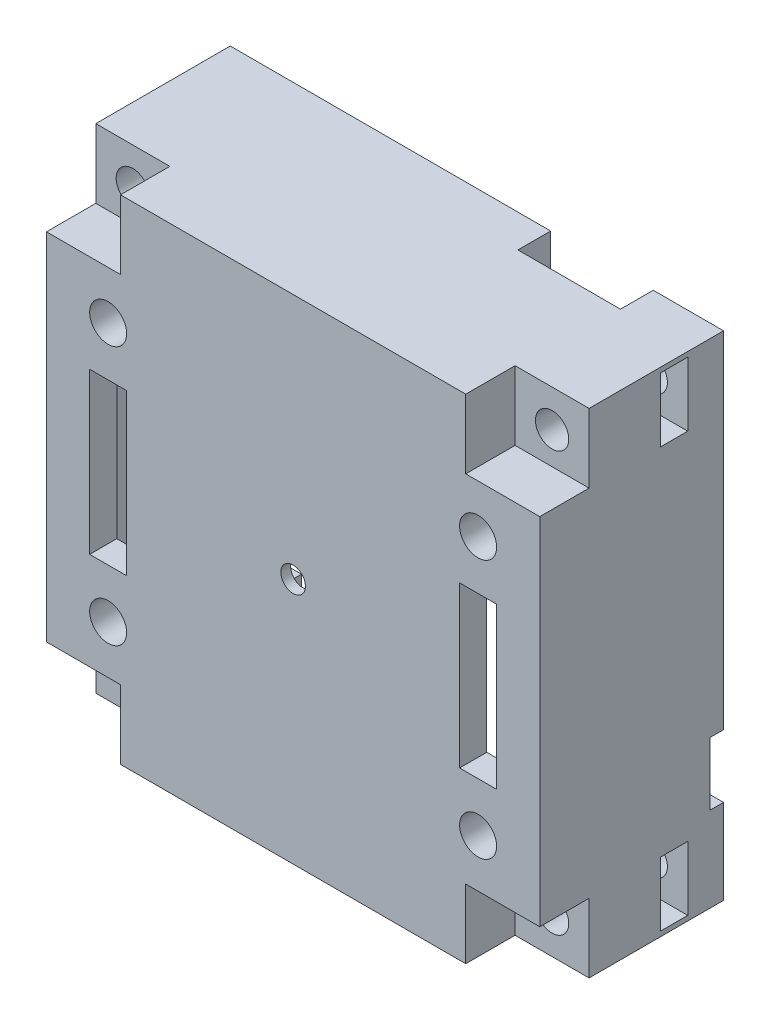
SolidWorks part; units mm, degrees
ref_plane "前视基准面" through (0, 0, 0) normal (0, 0, 1) x (1, 0, 0)
ref_plane "上视基准面" through (0, 0, 0) normal (0, 1, 0) x (1, 0, 0)
ref_plane "右视基准面" through (0, 0, 0) normal (1, 0, 0) x (0, 0, -1)
ref_plane "基准面1" through (0, 0, -12.4) normal (0, 0, -1) x (-1, 0, 0)
sketch "草图1" plane through (0, 0, -12.4) normal (0, 0, -1) x (-1, 0, 0)
  line L0 (1.7705, -8.8673) -> (1.7705, 31.1327)
  line L1 (1.7705, 31.1327) -> (-38.2295, 31.1327)
  line L2 (-38.2295, 31.1327) -> (-38.2295, -8.8673)
  line L3 (-38.2295, -8.8673) -> (1.7705, -8.8673)
  point P6 (-18.2295, 11.1327)
extrude "凸台-拉伸1" add sketch "草图1" against normal blind 12.7
ref_plane "基准面2" through (0, 0, -8) normal (0, 0, 1) x (1, 0, 0)
sketch "草图2" plane through (0, 0, -8) normal (0, 0, 1) x (1, 0, 0)
  line L0 (-2.0183, -8.4692) -> (2.7317, -8.4692)
  line L1 (2.7317, -8.4692) -> (4.2317, -5.8712)
  line L2 (4.2317, -5.8712) -> (2.7295, -3.2692)
  line L3 (2.7295, -3.2692) -> (-2.0183, -3.2692)
  line L4 (-2.0183, -3.2692) -> (-2.0183, -8.4692)
  line L5 (-1.7705, -8.8673) -> (-1.7705, 31.1327) construction
  line L6 (38.2295, -8.8673) -> (-1.7705, -8.8673) construction
  line L7 (2.7317, -8.4692) -> (-2.4592, 0.5217) construction
  line L9 (18.2295, 53.4111) -> (18.2295, -31.5909) construction
  line L10 (63.1299, 11.1327) -> (-18.8321, 11.1327) construction
  line L11 (-2.0183, 25.5346) -> (-2.0183, 30.7346)
  line L12 (2.7295, 25.5346) -> (-2.0183, 25.5346)
  line L13 (38.4773, 30.7346) -> (33.7273, 30.7346)
  line L14 (33.7273, 30.7346) -> (32.2273, 28.1365)
  line L15 (32.2273, 28.1365) -> (33.7295, 25.5346)
  line L16 (33.7295, 25.5346) -> (38.4773, 25.5346)
  line L21 (4.2317, 28.1365) -> (2.7295, 25.5346)
  line L22 (2.7317, 30.7346) -> (4.2317, 28.1365)
  line L23 (-2.0183, 30.7346) -> (2.7317, 30.7346)
  line L24 (38.4773, 25.5346) -> (38.4773, 30.7346)
  line L25 (38.4773, -3.2692) -> (38.4773, -8.4692)
  line L26 (33.7295, -3.2692) -> (38.4773, -3.2692)
  line L27 (32.2273, -5.8712) -> (33.7295, -3.2692)
  line L28 (33.7273, -8.4692) -> (32.2273, -5.8712)
  line L29 (38.4773, -8.4692) -> (33.7273, -8.4692)
  line L30 (-2.5019, -12.3303) -> (2.7295, -3.2692) construction
  point P26 (1.2295, -5.8673)
  point P34 (1.2295, -5.8673)
  dimension "D2" = 3
  dimension "D3" = 3
  dimension "D4" = 60
  dimension "D5" = 60
  dimension "D6" = 4.75
  dimension "D8" = 120
  dimension "D9" = 120
  dimension "D11" = 5.2
  dimension "D13" = 3
extrude "切除-拉伸2" cut sketch "草图2" against normal blind 1.5 and the other way blind 0.7
ref_plane "基准面3" through (0, 0, -5) normal (0, 0, -1) x (-1, 0, 0)
sketch "草图8" plane through (0, 0, -12.4) normal (0, 0, -1) x (-1, 0, 0)
  line L0 (-0.0295, 25.3327) -> (-36.4295, 25.3327)
  line L1 (-36.4295, 25.3327) -> (-36.4295, -3.0673)
  line L2 (-36.4295, -3.0673) -> (-0.0295, -3.0673)
  line L3 (-0.0295, -3.0673) -> (-0.0295, 25.3327)
extrude "切除-拉伸4" cut sketch "草图8" against normal up to surface (12.7 mm away) up to face at (18.2295, 11.1327, 0.3)
sketch "草图10" plane through (0, 0, 0.3) normal (0, 0, 1) x (1, 0, 0)
  line L1 (0.0295, 25.3327) -> (0.0295, -3.0673) construction
  line L2 (0.0295, -3.0673) -> (36.4295, -3.0673) construction
  line L3 (-1.7705, 25.5346) -> (4.2317, 25.5346)
  line L9 (36.4295, 25.3327) -> (0.0295, -3.0673) construction
  line L10 (36.4295, -3.0673) -> (0.0295, 25.3327) construction
  line L15 (36.4295, 25.3327) -> (0.0295, -3.0673) construction
  line L16 (36.4295, -3.0673) -> (0.0295, 25.3327) construction
  line L17 (4.2317, 25.5346) -> (4.2317, 31.1327)
  line L18 (-1.7705, 31.1327) -> (38.2295, 31.1327) construction
  line L19 (4.2317, 31.1327) -> (32.2273, 31.1327)
  line L20 (-1.7705, 25.5346) -> (-1.7705, -3.2692)
  line L21 (38.2295, 31.1327) -> (38.2295, -8.8673) construction
  line L31 (32.2273, 25.5346) -> (32.2273, 31.1327)
  line L48 (40.0436, 11.1327) -> (-13.5796, 11.1327) construction
  line L53 (22.8295, 16.6327) -> (13.6295, 5.6327) construction
  line L54 (22.8295, 5.6327) -> (13.6295, 16.6327) construction
  line L55 (1.7295, 17.6327) -> (4.7295, 17.6327)
  line L56 (18.2295, 36.1745) -> (18.2295, -22.808) construction
  line L57 (1.7295, 4.6327) -> (1.7295, 17.6327)
  line L58 (4.7295, 4.6327) -> (1.7295, 4.6327)
  line L59 (4.7295, 17.6327) -> (4.7295, 4.6327)
  line L60 (31.7295, 17.6327) -> (31.7295, 4.6327)
  line L61 (31.7295, 4.6327) -> (34.7295, 4.6327)
  line L62 (34.7295, 4.6327) -> (34.7295, 17.6327)
  line L63 (34.7295, 17.6327) -> (31.7295, 17.6327)
  line L64 (3.2295, 0.6327) -> (3.2295, 21.6327) construction
  line L65 (38.2295, 25.5346) -> (32.2273, 25.5346)
  line L66 (38.2295, 25.5346) -> (38.2295, -3.2692)
  line L67 (-1.7705, -3.2692) -> (4.2317, -3.2692)
  line L68 (4.2317, -3.2692) -> (4.2317, -8.8673)
  line L69 (4.2317, -8.8673) -> (32.2273, -8.8673)
  line L70 (32.2273, -3.2692) -> (32.2273, -8.8673)
  line L71 (38.2295, -3.2692) -> (32.2273, -3.2692)
  line L72 (17.7295, 10.6327) -> (18.7295, 11.6327) construction
  line L73 (17.7295, 11.6327) -> (18.7295, 10.6327) construction
  circle A0 centre (18.2295, 11.1327) radius 0.5
  circle A16 centre (3.2295, 0.6327) radius 1.5
  circle A17 centre (3.2295, 21.6327) radius 1.5
  circle A18 centre (33.2295, 21.6327) radius 1.5
  circle A19 centre (33.2295, 0.6327) radius 1.5
  point P11 (18.2295, 11.1327)
  point P12 (18.2295, 11.1327)
  point P13 (18.2295, 11.1327)
  point P25 (18.2295, 31.1327)
  point P26 (18.2295, 11.1327)
  point P33 (-1.7705, 11.1327)
  point P42 (38.2295, 11.1327)
  dimension "D5" = 13
  dimension "D6" = 3
  dimension "D7" = 3
  dimension "D11" = 1
  dimension "D1" = 21
  dimension "D2" = 30
  dimension "D3" = 11
  dimension "D4" = 9.2
  dimension "D8" = 3
  dimension "D9" = 1
  dimension "D10" = 1
extrude "凸台-拉伸2" add sketch "草图10" along normal blind 2.2 separate body
sketch "草图13" plane through (0, 0, -12.4) normal (0, 0, -1) x (-1, 0, 0)
  line L0 (10.4025, 11.1327) -> (-53.3827, 11.1327) construction
  line L3 (-18.2295, -16.9604) -> (-18.2295, 39.7747) construction
  circle A0 centre (-35.2295, -5.8673) radius 1.35
  circle A1 centre (-1.2295, -5.8673) radius 1.35
  circle A2 centre (-1.2295, 28.1327) radius 1.35
  circle A3 centre (-35.2295, 28.1327) radius 1.35
  dimension "D2" = 2.7
extrude "切除-拉伸6" cut sketch "草图13" against normal up to surface (12.7 mm away) up to face at (18.2295, 11.1327, 0.3)
fillet "圆角1" radius 1 4 edges at (36.4295, 25.3327, -6.05) (36.4295, -3.0673, -6.05) (0.0295, -3.0673, -6.05) (0.0295, 25.3327, -6.05)
sketch "草图14" plane through (0, -8.8673, 0) normal (0, -1, 0) x (1, 0, 0)
  line L0 (38.2295, -12.4) -> (-1.7705, -12.4) construction
  line L8 (4.0099, -12.4) -> (12.3299, -12.4)
  line L9 (12.3299, -12.4) -> (12.3299, -9.75)
  line L10 (12.3299, -9.75) -> (4.0099, -9.75)
  line L11 (4.0099, -9.75) -> (4.0099, -12.4)
extrude "切除-拉伸8" cut sketch "草图14" against normal up to next (5.8 mm away)
sketch "草图15" plane through (0, -8.8673, 0) normal (0, -1, 0) x (1, 0, 0)
  line L0 (17.3459, -12.4) -> (30.2459, -12.4)
  line L1 (38.2295, -12.4) -> (12.3299, -12.4) construction
  line L3 (30.2459, -5.1) -> (17.3459, -5.1)
  line L4 (30.2459, -5.1) -> (30.2459, -12.4)
  line L28 (17.3459, -5.1) -> (17.3459, -12.4)
  dimension "D1" = 7.3
extrude "切除-拉伸9" cut sketch "草图15" against normal up to next (5.8 mm away)
sketch "草图16" plane through (38.2295, 0, 0) normal (1, 0, 0) x (0, 0, -1)
  line L0 (12.4, -1.9836) -> (11.3145, -1.9836)
  line L1 (12.4, 31.1327) -> (12.4, -8.8673) construction
  line L2 (11.3145, -1.9836) -> (11.3145, 3.1167)
  line L3 (11.3145, 3.1167) -> (12.4, 3.1167)
  line L4 (12.4, 3.1167) -> (12.4, -1.9836)
extrude "切除-拉伸10" cut sketch "草图16" against normal up to next (1.8 mm away)
sketch "草图17" plane through (0, 31.1327, 0) normal (0, 1, 0) x (1, 0, 0)
  line L0 (32.533, 12.4) -> (32.533, 9.7407)
  line L1 (-1.7705, 12.4) -> (38.2295, 12.4) construction
  line L2 (24.213, 12.4) -> (32.533, 12.4)
  line L3 (24.213, 12.4) -> (24.213, 9.7407)
  line L10 (24.213, 9.7407) -> (32.533, 9.7407)
extrude "切除-拉伸11" cut sketch "草图17" against normal up to next (5.8 mm away)
ref_axis "基准轴1" through (18.2295, 11.1327, 2.5) along (0, 0, -1)
ref_plane "基准面4" through (0, 11.1327, 0) normal (0, -1, 0) x (-1, 0, 0)
sketch "草图23" plane through (0, 0, 2.5) normal (0, 0, 1) x (1, 0, 0)
  line L0 (32.2273, 25.5346) -> (32.2273, 31.1327)
  line L1 (32.2273, 31.1327) -> (38.2295, 31.1327)
  line L2 (38.2295, 31.1327) -> (38.2295, 25.5346)
  line L3 (38.2295, 25.5346) -> (32.2273, 25.5346)
  line L4 (32.2273, -3.2692) -> (32.2273, -8.8673)
  line L5 (32.2273, -8.8673) -> (32.2273, -3.2692) construction
  line L6 (4.2317, -8.8673) -> (32.2273, -8.8673) construction
  line L7 (32.2273, -8.8673) -> (38.2295, -8.8673)
  line L8 (38.2295, -8.8673) -> (38.2295, -3.2692)
  line L9 (32.2273, -3.2692) -> (38.2295, -3.2692) construction
  line L10 (38.2295, -3.2692) -> (38.2295, 25.5346) construction
  line L11 (38.2295, -3.2692) -> (32.2273, -3.2692)
  line L12 (4.2317, -8.8673) -> (4.2317, -3.2692)
  line L13 (4.2317, -3.2692) -> (-1.7705, -3.2692)
  line L14 (-1.7705, -3.2692) -> (-1.7705, -8.8673)
  line L15 (-1.7705, -8.8673) -> (4.2317, -8.8673)
  line L16 (4.2317, 25.5346) -> (-1.7705, 25.5346)
  line L17 (4.2317, 25.5346) -> (-1.7705, 25.5346) construction
  line L18 (-1.7705, 25.5346) -> (-1.7705, 31.1327)
  line L19 (-1.7705, 31.1327) -> (4.2317, 31.1327)
  line L20 (4.2317, 31.1327) -> (4.2317, 25.5346)
extrude "切除-拉伸12" cut sketch "草图23" against normal blind 4
sketch "草图24" plane through (0, 0, 0.3) normal (0, 0, -1) x (-1, 0, 0)
  line L1 (-12.7295, 18.1327) -> (-23.7295, 18.1327)
  line L2 (-12.7295, 18.1327) -> (-12.7295, 4.1327)
  line L3 (-12.7295, 4.1327) -> (-23.7295, 4.1327)
  line L4 (-23.7295, 18.1327) -> (-23.7295, 4.1327)
  line L5 (-12.7295, 18.1327) -> (-23.7295, 4.1327) construction
  line L6 (-12.7295, 4.1327) -> (-23.7295, 18.1327) construction
  circle A0 centre (-18.2295, 11.1327) radius 0.5 construction
  point P11 (-18.2295, 11.1327)
  dimension "D1" = 14
  dimension "D2" = 11
extrude "切除-拉伸14" cut sketch "草图24" against normal blind 1.4
sketch "草图22" plane through (0, 11.1327, 0) normal (0, -1, 0) x (-1, 0, 0)
  line L0 (-19.2295, -1.7) -> (-19.2295, -2.5)
  line L1 (-19.2295, -2.5) -> (-18.2295, -2.5)
  line L3 (-19.2295, -1.7) -> (-18.2295, -1.7)
  line L5 (-18.2295, -5.0619) -> (-18.2295, 2.0112) construction
  line L6 (-18.2295, -2.5) -> (-18.2295, -1.7)
  line L11 (-17.7295, -1.7) -> (-18.7295, -1.7) construction
  line L12 (-34.7295, -2.5) -> (-31.7295, -2.5) construction
  line L16 (-18.7295, -2.5) -> (-17.7295, -2.5) construction
  dimension "D2" = 1
revolve "切除-旋转3" cut sketch "草图22" angle 360 about L5
combine bodies "组合1" operation type add bodies to combine 152 153
